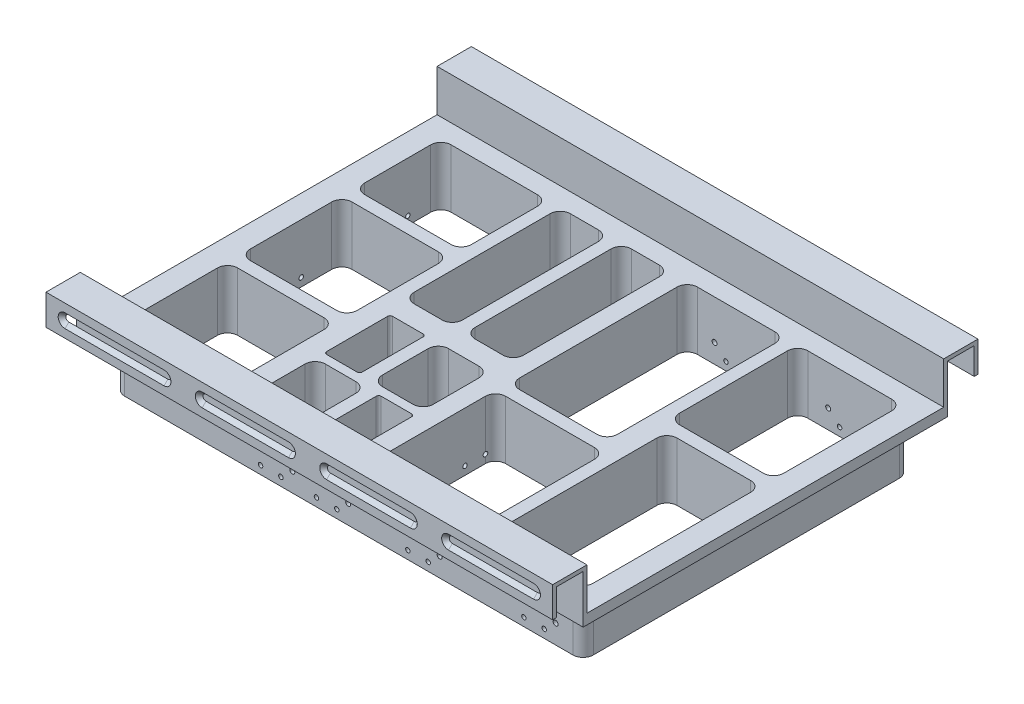
SolidWorks part; units mm, degrees
ref_plane "Front Plane" through (0, 0, 0) normal (0, 0, 1) x (1, 0, 0)
ref_plane "Top Plane" through (0, 0, 0) normal (0, 1, 0) x (1, 0, 0)
ref_plane "Right Plane" through (0, 0, 0) normal (1, 0, 0) x (0, 0, -1)
sketch "Sketch1" plane through (0, 0, 0) normal (0, 1, 0) x (1, 0, 0)
  line L1 (199.5, -143.5) -> (-199.5, -143.5)
  line L2 (199.5, -143.5) -> (199.5, 143.5)
  line L3 (199.5, 143.5) -> (-199.5, 143.5)
  line L4 (-199.5, -143.5) -> (-199.5, 143.5)
  line L5 (199.5, -143.5) -> (-199.5, 143.5) construction
  line L6 (199.5, 143.5) -> (-199.5, -143.5) construction
  point P0 (0, 0)
  dimension "D1" = 399
  dimension "D2" = 287
extrude "Boss-Extrude1" add sketch "Sketch1" along normal blind 53
sketch "Sketch3" plane through (0, 0, 0) normal (0, -1, 0) x (-1, 0, 0)
  line L23 (184.5, -128.5) -> (184.5, 128.5)
  line L24 (184.5, 128.5) -> (-184.5, 128.5)
  line L25 (-184.5, 128.5) -> (-184.5, -128.5)
  line L26 (-184.5, -128.5) -> (184.5, -128.5)
  line L27 (184.5, -128.5) -> (184.5, 128.5)
  line L28 (184.5, 128.5) -> (-184.5, 128.5)
  line L29 (-184.5, 128.5) -> (-184.5, -128.5)
  line L30 (-184.5, -128.5) -> (184.5, -128.5)
  dimension "D1" = 15
extrude "Cut-Extrude2" cut sketch "Sketch3" against normal blind 45 flip side to cut
sketch "Sketch2" plane through (0, 53, 0) normal (0, 1, 0) x (1, 0, 0)
  line L1 (-173.5, -125.5) -> (-105.5, -125.5)
  line L2 (-181.5, -117.5) -> (-181.5, -50.5)
  line L3 (-173.5, -42.5) -> (-105.5, -42.5)
  line L4 (-97.5, -117.5) -> (-97.5, -50.5)
  line L5 (-173.5, -32.5) -> (-105.5, -32.5)
  line L6 (-181.5, -24.5) -> (-181.5, 39.5)
  line L7 (-173.5, 47.5) -> (-105.5, 47.5)
  line L8 (-181.5, 125.5) -> (-181.5, -125.5)
  line L9 (-181.5, -125.5) -> (181.5, -125.5)
  line L10 (181.5, -125.5) -> (181.5, 125.5)
  line L11 (181.5, 125.5) -> (-181.5, 125.5)
  line L12 (-181.5, 125.5) -> (-181.5, -125.5) construction
  line L13 (-181.5, -125.5) -> (181.5, -125.5) construction
  line L14 (181.5, -125.5) -> (181.5, 125.5) construction
  line L15 (181.5, 125.5) -> (-181.5, 125.5) construction
  line L16 (-97.5, -24.5) -> (-97.5, 39.5)
  line L17 (-173.5, 125.5) -> (-105.5, 125.5)
  line L18 (-181.5, 117.5) -> (-181.5, 65.5)
  line L19 (-173.5, 57.5) -> (-105.5, 57.5)
  line L20 (-97.5, 117.5) -> (-97.5, 65.5)
  line L21 (173.5, -125.5) -> (115.5, -125.5)
  line L22 (181.5, -117.5) -> (181.5, 6.5)
  line L23 (173.5, 14.5) -> (115.5, 14.5)
  line L24 (107.5, -117.5) -> (107.5, 6.5)
  line L25 (173.5, 125.5) -> (107.5, 125.5)
  line L26 (181.5, 117.5) -> (181.5, 32.5)
  line L27 (173.5, 24.5) -> (107.5, 24.5)
  line L28 (99.5, 117.5) -> (99.5, 32.5)
  line L29 (81.5, 125.5) -> (20.5, 125.5)
  line L30 (89.5, 117.5) -> (89.5, -6.5)
  line L31 (81.5, -14.5) -> (20.5, -14.5)
  line L32 (12.5, 117.5) -> (12.5, -6.5)
  line L33 (-9.5, 125.5) -> (-31.5, 125.5)
  line L34 (-1.5, 117.5) -> (-1.5, 10.5)
  line L35 (-9.5, 2.5) -> (-31.5, 2.5)
  line L36 (-39.5, 117.5) -> (-39.5, 10.5)
  line L37 (-57.5, 125.5) -> (-79.5, 125.5)
  line L38 (-49.5, 117.5) -> (-49.5, 10.5)
  line L39 (-57.5, 2.5) -> (-79.5, 2.5)
  line L40 (-87.5, 117.5) -> (-87.5, 10.5)
  line L41 (-79.5, -14.5) -> (-55.5, -14.5)
  line L42 (-81.5, -16.5) -> (-81.5, -64.5)
  line L43 (-79.5, -66.5) -> (-55.5, -66.5)
  line L44 (-53.5, -16.5) -> (-53.5, -64.5)
  line L45 (-73.5, -125.5) -> (-49.5, -125.5)
  line L46 (-81.5, -117.5) -> (-81.5, -81.5)
  line L47 (-73.5, -73.5) -> (-49.5, -73.5)
  line L48 (-41.5, -117.5) -> (-41.5, -81.5)
  line L49 (-35.5, -14.5) -> (-11.5, -14.5)
  line L50 (-43.5, -22.5) -> (-43.5, -58.5)
  line L51 (-35.5, -66.5) -> (-11.5, -66.5)
  line L52 (-3.5, -22.5) -> (-3.5, -58.5)
  line L53 (-29.5, -73.5) -> (-5.5, -73.5)
  line L54 (-31.5, -75.5) -> (-31.5, -123.5)
  line L55 (-29.5, -125.5) -> (-5.5, -125.5)
  line L56 (-3.5, -75.5) -> (-3.5, -123.5)
  line L57 (89.5, -125.5) -> (19.5, -125.5)
  line L58 (97.5, -117.5) -> (97.5, -32.5)
  line L59 (89.5, -24.5) -> (19.5, -24.5)
  line L60 (11.5, -117.5) -> (11.5, -32.5)
  arc A0 (-79.5, 125.5) -> (-87.5, 117.5) centre (-79.5, 117.5) ccw
  arc A1 (-79.5, 2.5) -> (-87.5, 10.5) centre (-79.5, 10.5) cw
  arc A2 (-49.5, 10.5) -> (-57.5, 2.5) centre (-57.5, 10.5) cw
  arc A3 (-57.5, 125.5) -> (-49.5, 117.5) centre (-57.5, 117.5) cw
  arc A4 (-31.5, 125.5) -> (-39.5, 117.5) centre (-31.5, 117.5) ccw
  arc A5 (-31.5, 2.5) -> (-39.5, 10.5) centre (-31.5, 10.5) cw
  arc A6 (-1.5, 10.5) -> (-9.5, 2.5) centre (-9.5, 10.5) cw
  arc A7 (-9.5, 125.5) -> (-1.5, 117.5) centre (-9.5, 117.5) cw
  arc A8 (20.5, 125.5) -> (12.5, 117.5) centre (20.5, 117.5) ccw
  arc A9 (20.5, -14.5) -> (12.5, -6.5) centre (20.5, -6.5) cw
  arc A10 (89.5, -6.5) -> (81.5, -14.5) centre (81.5, -6.5) cw
  arc A11 (81.5, 125.5) -> (89.5, 117.5) centre (81.5, 117.5) cw
  arc A12 (107.5, 125.5) -> (99.5, 117.5) centre (107.5, 117.5) ccw
  arc A13 (173.5, 125.5) -> (181.5, 117.5) centre (173.5, 117.5) cw
  arc A14 (181.5, 32.5) -> (173.5, 24.5) centre (173.5, 32.5) cw
  arc A15 (107.5, 24.5) -> (99.5, 32.5) centre (107.5, 32.5) cw
  arc A16 (115.5, 14.5) -> (107.5, 6.5) centre (115.5, 6.5) ccw
  arc A17 (181.5, 6.5) -> (173.5, 14.5) centre (173.5, 6.5) ccw
  arc A18 (173.5, -125.5) -> (181.5, -117.5) centre (173.5, -117.5) ccw
  arc A19 (115.5, -125.5) -> (107.5, -117.5) centre (115.5, -117.5) cw
  arc A20 (89.5, -125.5) -> (97.5, -117.5) centre (89.5, -117.5) ccw
  arc A21 (97.5, -32.5) -> (89.5, -24.5) centre (89.5, -32.5) ccw
  arc A22 (19.5, -24.5) -> (11.5, -32.5) centre (19.5, -32.5) ccw
  arc A23 (19.5, -125.5) -> (11.5, -117.5) centre (19.5, -117.5) cw
  arc A28 (-43.5, -58.5) -> (-35.5, -66.5) centre (-35.5, -58.5) ccw
  arc A29 (-11.5, -66.5) -> (-3.5, -58.5) centre (-11.5, -58.5) ccw
  arc A30 (-11.5, -14.5) -> (-3.5, -22.5) centre (-11.5, -22.5) cw
  arc A31 (-35.5, -14.5) -> (-43.5, -22.5) centre (-35.5, -22.5) ccw
  arc A36 (-49.5, -73.5) -> (-41.5, -81.5) centre (-49.5, -81.5) cw
  arc A37 (-49.5, -125.5) -> (-41.5, -117.5) centre (-49.5, -117.5) ccw
  arc A38 (-73.5, -125.5) -> (-81.5, -117.5) centre (-73.5, -117.5) cw
  arc A39 (-81.5, -81.5) -> (-73.5, -73.5) centre (-73.5, -81.5) cw
  arc A40 (-105.5, -42.5) -> (-97.5, -50.5) centre (-105.5, -50.5) cw
  arc A41 (-105.5, -125.5) -> (-97.5, -117.5) centre (-105.5, -117.5) ccw
  arc A42 (-173.5, -125.5) -> (-181.5, -117.5) centre (-173.5, -117.5) cw
  arc A43 (-181.5, -50.5) -> (-173.5, -42.5) centre (-173.5, -50.5) cw
  arc A44 (-105.5, 47.5) -> (-97.5, 39.5) centre (-105.5, 39.5) cw
  arc A45 (-105.5, -32.5) -> (-97.5, -24.5) centre (-105.5, -24.5) ccw
  arc A46 (-173.5, -32.5) -> (-181.5, -24.5) centre (-173.5, -24.5) cw
  arc A47 (-181.5, 39.5) -> (-173.5, 47.5) centre (-173.5, 39.5) cw
  arc A48 (-105.5, 125.5) -> (-97.5, 117.5) centre (-105.5, 117.5) cw
  arc A49 (-105.5, 57.5) -> (-97.5, 65.5) centre (-105.5, 65.5) ccw
  arc A50 (-181.5, 65.5) -> (-173.5, 57.5) centre (-173.5, 65.5) ccw
  arc A51 (-173.5, 125.5) -> (-181.5, 117.5) centre (-173.5, 117.5) ccw
  arc A52 (-81.5, -16.5) -> (-79.5, -14.5) centre (-79.5, -16.5) cw
  arc A53 (-79.5, -66.5) -> (-81.5, -64.5) centre (-79.5, -64.5) cw
  arc A54 (-53.5, -64.5) -> (-55.5, -66.5) centre (-55.5, -64.5) cw
  arc A55 (-55.5, -14.5) -> (-53.5, -16.5) centre (-55.5, -16.5) cw
  arc A56 (-3.5, -75.5) -> (-5.5, -73.5) centre (-5.5, -75.5) ccw
  arc A57 (-5.5, -125.5) -> (-3.5, -123.5) centre (-5.5, -123.5) ccw
  arc A58 (-31.5, -123.5) -> (-29.5, -125.5) centre (-29.5, -123.5) ccw
  arc A59 (-31.5, -75.5) -> (-29.5, -73.5) centre (-29.5, -75.5) cw
  point P54 (-87.5, 125.5)
  point P57 (-87.5, 2.5)
  point P62 (-49.5, 125.5)
  point P65 (-39.5, 125.5)
  point P72 (-1.5, 125.5)
  point P75 (12.5, 125.5)
  point P82 (89.5, 125.5)
  point P85 (99.5, 125.5)
  point P91 (181.5, 24.5)
  point P103 (107.5, -125.5)
  point P106 (97.5, -125.5)
  point P109 (97.5, -24.5)
  point P114 (11.5, -125.5)
  point P119 (-3.5, -125.5)
  point P122 (-31.5, -125.5)
  point P127 (-43.5, -66.5)
  point P130 (-3.5, -66.5)
  point P139 (-81.5, -14.5)
  point P142 (-81.5, -66.5)
  point P149 (-41.5, -125.5)
  point P152 (-81.5, -125.5)
  point P155 (-81.5, -73.5)
  point P171 (-181.5, -32.5)
  point P174 (-181.5, 47.5)
  point P177 (-97.5, 125.5)
  point P182 (-181.5, 57.5)
  point P188 (-81.5, -14.5)
  point P191 (-81.5, -66.5)
  point P200 (-3.5, -125.5)
  point P203 (-31.5, -125.5)
  dimension "D31" = 8
  dimension "D32" = 8
  dimension "D33" = 8
  dimension "D34" = 2
  dimension "D35" = 2
  dimension "D2" = 74
  dimension "D3" = 82
  dimension "D4" = 101
  dimension "D5" = 10
  dimension "D6" = 86
  dimension "D7" = 10
  dimension "D8" = 15
  dimension "D9" = 28
  dimension "D10" = 40
  dimension "D11" = 52
  dimension "D12" = 52
  dimension "D13" = 77
  dimension "D14" = 38
  dimension "D15" = 38
  dimension "D16" = 84
  dimension "D17" = 68
  dimension "D18" = 80
  dimension "D19" = 10
  dimension "D20" = 10
  dimension "D21" = 7
  dimension "D22" = 10
  dimension "D23" = 101
  dimension "D24" = 10
  dimension "D25" = 10
  dimension "D26" = 123
  dimension "D27" = 10
  dimension "D28" = 10
  dimension "D29" = 40
  dimension "D30" = 10
  dimension "D1" = 18
extrude "Mini bin cuts" cut sketch "Sketch2" against normal blind 46
fillet "Fillet1" radius 8 4 edges at (-184.5, 22.5, -128.5) (184.5, 22.5, -128.5) (184.5, 22.5, 128.5) (-184.5, 22.5, 128.5)
sketch "Sketch6" plane through (-184.5, 0, 0) normal (-1, 0, 0) x (0, 0, 1)
  line L0 (128.5, 45) -> (128.5, 0) construction
  line L1 (-128.5, 0) -> (128.5, 0)
  line L2 (-128.5, 0) -> (-128.5, 7)
  line L3 (-128.5, 7) -> (128.5, 7)
  line L4 (128.5, 0) -> (128.5, 7)
  dimension "D1" = 7
extrude "Cut-Extrude5" cut sketch "Sketch6" against normal through all
sketch "Sketch7" plane through (-184.5, 0, 0) normal (-1, 0, 0) x (0, 0, 1)
  line L0 (-120.5, 13.5) -> (120.5, 13.5) construction
  line L1 (-120.5, 45) -> (-120.5, 7) construction
  line L2 (120.5, 7) -> (120.5, 45) construction
  line L3 (120.5, 7) -> (-120.5, 7) construction
  line L4 (-91.5, 13.5) -> (-91.5, 45) construction
  line L5 (120.5, 45) -> (-120.5, 45) construction
  line L6 (-7.5, 13.5) -> (-7.5, 45) construction
  line L7 (84, 13.5) -> (84, 45) construction
  circle A0 centre (-99.5, 13.5) radius 1.75
  circle A1 centre (-83.5, 13.5) radius 1.75
  circle A2 centre (-15.5, 13.5) radius 1.75
  circle A3 centre (76, 13.5) radius 1.75
  circle A4 centre (0.5, 13.5) radius 1.75
  circle A5 centre (92, 13.5) radius 1.75
  circle A6 centre (-74.5, 21.963) radius 1.95
  circle A7 centre (101, 21.963) radius 1.95
  circle A8 centre (9.5, 21.963) radius 1.95
  dimension "D2" = 36.5
  dimension "D5" = 3.5
  dimension "D7" = 3.5
  dimension "D9" = 3.5
  dimension "D11" = 3.9
  dimension "D12" = 3.9
  dimension "D13" = 3.9
  dimension "D1" = 6.5
  dimension "D3" = 29
  dimension "D4" = 113
  dimension "D6" = 8
  dimension "D8" = 8
  dimension "D10" = 8
  dimension "D14" = 17
  dimension "D15" = 17
  dimension "D16" = 17
  dimension "D17" = 8.463
  dimension "D18" = 8.463
  dimension "D19" = 8.463
extrude "Holes Lids 1,2,3" cut sketch "Sketch7" against normal up to surface (3 mm away) up to face at (-181.5, 30, 84)
sketch "Sketch8" plane through (0, 0, 128.5) normal (0, 0, 1) x (1, 0, 0)
  line L0 (-176.5, 13.5) -> (176.5, 13.5) construction
  line L1 (-176.5, 45) -> (-176.5, 7) construction
  line L2 (176.5, 7) -> (176.5, 45) construction
  line L5 (-61.5, 45) -> (-61.5, 7) construction
  line L6 (176.5, 45) -> (-176.5, 45) construction
  line L7 (176.5, 7) -> (-176.5, 7) construction
  line L8 (-17.5, 45) -> (-17.5, 7) construction
  line L11 (145.896, 45) -> (145.896, 7) construction
  line L12 (54.5, 45) -> (54.5, 7) construction
  circle A0 centre (-69.5, 13.5) radius 1.75
  circle A1 centre (-25.5, 13.5) radius 1.75
  circle A2 centre (46.5, 13.5) radius 1.75
  circle A3 centre (137.896, 13.5) radius 1.75
  circle A4 centre (153.896, 13.5) radius 1.75
  circle A5 centre (62.5, 13.5) radius 1.75
  circle A6 centre (-9.5, 13.5) radius 1.75
  circle A7 centre (-53.5, 13.5) radius 1.75
  circle A8 centre (-44.5, 21.96) radius 1.95
  circle A9 centre (-0.5, 21.96) radius 1.95
  circle A10 centre (71.5, 21.96) radius 1.95
  circle A11 centre (162.896, 21.96) radius 1.95
  dimension "D5" = 3.5
  dimension "D6" = 3.5
  dimension "D7" = 3.5
  dimension "D8" = 3.5
  dimension "D14" = 3.9
  dimension "D16" = 8.46
  dimension "D17" = 17
  dimension "D18" = 8.46
  dimension "D19" = 17
  dimension "D20" = 8.46
  dimension "D22" = 8.46
  dimension "D1" = 115
  dimension "D2" = 159
  dimension "D3" = 6.5
  dimension "D4" = 122
  dimension "D9" = 8
  dimension "D10" = 8
  dimension "D11" = 8
  dimension "D12" = 8
  dimension "D13" = 30.604
  dimension "D15" = 17
  dimension "D21" = 17
extrude "Holes Lids 8,9,12,13" cut sketch "Sketch8" against normal up to surface (3 mm away) up to face at (54.5, 30, 125.5)
sketch "Sketch9" plane through (0, 0, -128.5) normal (0, 0, -1) x (-1, 0, 0)
  line L0 (-176.5, 13.5) -> (176.5, 13.5) construction
  line L1 (-176.5, 45) -> (-176.5, 7) construction
  line L2 (176.5, 7) -> (176.5, 45) construction
  line L3 (-140.5, 45) -> (-140.5, 7) construction
  line L4 (176.5, 45) -> (-176.5, 45) construction
  line L5 (-176.5, 7) -> (176.5, 7) construction
  line L7 (20.5, 45) -> (20.5, 7) construction
  line L8 (199.5, 45) -> (-199.5, 45) construction
  line L9 (68.5, 45) -> (68.5, 7) construction
  line L10 (-51, 45) -> (-51, 7) construction
  circle A0 centre (-148.5, 13.5) radius 1.75
  circle A1 centre (-59, 13.5) radius 1.75
  circle A2 centre (12.5, 13.5) radius 1.75
  circle A3 centre (60.5, 13.5) radius 1.75
  circle A4 centre (-132.5, 13.5) radius 1.75
  circle A5 centre (-43, 13.5) radius 1.75
  circle A6 centre (28.5, 13.5) radius 1.75
  circle A7 centre (76.5, 13.5) radius 1.75
  circle A8 centre (-123.5, 21.96) radius 1.95
  circle A9 centre (-34, 21.96) radius 1.95
  circle A10 centre (37.5, 21.96) radius 1.95
  circle A11 centre (85.5, 21.96) radius 1.95
  dimension "D6" = 3.5
  dimension "D10" = 8
  dimension "D11" = 3.5
  dimension "D12" = 3.5
  dimension "D13" = 3.5
  dimension "D14" = 3.9
  dimension "D15" = 3.9
  dimension "D16" = 3.9
  dimension "D17" = 17
  dimension "D19" = 17
  dimension "D20" = 8.46
  dimension "D21" = 8.46
  dimension "D22" = 8.46
  dimension "D23" = 8.46
  dimension "D24" = 3.9
  dimension "D25" = 17
  dimension "D1" = 6.5
  dimension "D2" = 36
  dimension "D3" = 125.5
  dimension "D4" = 197
  dimension "D5" = 245
  dimension "D7" = 8
  dimension "D8" = 8
  dimension "D9" = 8
  dimension "D18" = 17
extrude "Holes Lids 4,5,10,11" cut sketch "Sketch9" against normal up to surface (3 mm away) up to face at (51, 30, -125.5)
sketch "Sketch11" plane through (-3.5, 0, 0) normal (-1, 0, 0) x (0, 0, 1)
  line L0 (22.5, 13.5) -> (58.5, 13.5) construction
  line L1 (22.5, 7) -> (22.5, 53) construction
  line L2 (58.5, 7) -> (58.5, 53) construction
  line L3 (40.5, 7) -> (40.5, 53) construction
  line L4 (58.5, 7) -> (22.5, 7) construction
  line L5 (22.5, 53) -> (58.5, 53) construction
  circle A0 centre (32.5, 13.5) radius 1.75
  circle A1 centre (48.5, 13.5) radius 1.75
  dimension "D2" = 3.5
  dimension "D1" = 6.5
  dimension "D3" = 8
extrude "Hole Lid 7" cut sketch "Sketch11" against normal up to next
sketch "Sketch12" plane through (-81.5, 0, 0) normal (1, 0, 0) x (0, 0, -1)
  line L0 (-64.5, 13.5) -> (-16.5, 13.5) construction
  line L1 (-64.5, 7) -> (-64.5, 53) construction
  line L2 (-16.5, 7) -> (-16.5, 53) construction
  line L3 (-40.5, 7) -> (-40.5, 53) construction
  line L5 (-16.5, 7) -> (-64.5, 7) construction
  line L6 (-16.5, 53) -> (-64.5, 53) construction
  circle A0 centre (-48.5, 13.5) radius 1.75
  circle A1 centre (-32.5, 13.5) radius 1.75
  dimension "D2" = 3.5
  dimension "D1" = 6.5
  dimension "D3" = 8
extrude "Hole Lid 6" cut sketch "Sketch12" against normal blind 15
sketch "Sketch15" plane through (-199.5, 0, 0) normal (-1, 0, 0) x (0, 0, 1)
  line L0 (143.5, 53) -> (143.5, 83)
  line L1 (143.5, 83) -> (164.5, 83)
  line L2 (164.5, 83) -> (164.5, 62)
  line L3 (164.5, 62) -> (167.5, 62)
  line L4 (167.5, 62) -> (167.5, 86)
  line L5 (167.5, 86) -> (140.5, 86)
  line L6 (140.5, 86) -> (140.5, 53)
  line L7 (-143.5, 53) -> (143.5, 53) construction
  line L8 (140.5, 53) -> (143.5, 53)
  line L9 (0, 0) -> (0, 7) construction
  line L10 (120.5, 7) -> (-120.5, 7) construction
  line L11 (-140.5, 53) -> (-143.5, 53)
  line L12 (-140.5, 86) -> (-140.5, 53)
  line L13 (-167.5, 86) -> (-140.5, 86)
  line L14 (-167.5, 62) -> (-167.5, 86)
  line L15 (-164.5, 62) -> (-167.5, 62)
  line L16 (-164.5, 83) -> (-164.5, 62)
  line L17 (-143.5, 83) -> (-164.5, 83)
  line L18 (-143.5, 53) -> (-143.5, 83)
  dimension "D1" = 21
  dimension "D2" = 21
  dimension "D3" = 30
  dimension "D4" = 3
  dimension "D5" = 3
  dimension "D6" = 3
extrude "Boss-Extrude3" add sketch "Sketch15" against normal up to surface (399 mm away) up to face at (199.5, 49, 0)
sketch "Split Lines" plane through (0, 86, 0) normal (0, 1, 0) x (1, 0, 0)
  line L0 (-199.5, 0) -> (199.5, 0) construction
  line L1 (-97.5, 117.5) -> (-97.5, 65.5) construction
  line L2 (199.5, 140.5) -> (-199.5, 140.5) construction
  line L3 (-199.5, 140.5) -> (-199.5, -140.5) construction
  line L4 (199.5, -140.5) -> (199.5, 140.5) construction
  line L5 (-93.5, 167.5) -> (-93.5, 104.5)
  line L6 (199.5, 143.5) -> (-199.5, 143.5) construction
  line L7 (-199.5, -143.5) -> (199.5, -143.5) construction
  line L8 (-90.25, -114.5) -> (-91.5, -114.5)
  line L9 (-89.5, -117.75) -> (-89.5, -115.25)
  line L10 (-88.25, -118.5) -> (-88.75, -118.5)
  line L11 (-87.5, -105.25) -> (-87.5, -117.75)
  line L12 (-88.75, -104.5) -> (-88.25, -104.5)
  line L13 (-89.5, -107.75) -> (-89.5, -105.25)
  line L14 (-93.5, 45) -> (-92.5, 45)
  line L15 (-91.75, 45.75) -> (-91.75, 48.25)
  line L16 (-91, 49) -> (-90.5, 49)
  line L17 (-89.75, 48.25) -> (-89.75, 35.75)
  line L18 (-90.5, 35) -> (-91, 35)
  line L19 (-91.75, 35.75) -> (-91.75, 38.25)
  line L20 (-92.5, 39) -> (-93.5, 39)
  line L21 (-93.5, 39) -> (-93.5, -8)
  line L22 (-91.5, -167.5) -> (-91.5, -114.5)
  line L23 (-81.5, -117.5) -> (-81.5, -81.5) construction
  line L24 (-139.5, -32.5) -> (-139.5, -42.5) construction
  line L25 (-173.5, -42.5) -> (-105.5, -42.5) construction
  line L26 (-163.5, -37) -> (-163.5, -36)
  line L27 (-157.5, -36) -> (-157.5, -37)
  line L28 (-156.75, -37.75) -> (-154.25, -37.75)
  line L29 (-153.5, -38.5) -> (-153.5, -39)
  line L30 (-154.25, -39.75) -> (-166.75, -39.75)
  line L31 (-121.5, -36) -> (-121.5, -37)
  line L32 (-122.25, -37.75) -> (-124.75, -37.75)
  line L33 (-125.5, -38.5) -> (-125.5, -39)
  line L34 (-124.75, -39.75) -> (-112.25, -39.75)
  line L35 (-111.5, -39) -> (-111.5, -38.5)
  line L36 (-112.25, -37.75) -> (-114.75, -37.75)
  line L37 (-93.5, 98.5) -> (-93.5, 45)
  line L38 (-115.5, -37) -> (-115.5, -36)
  line L39 (6.5, 167.5) -> (6.5, 104.5)
  line L40 (-1.5, 117.5) -> (-1.5, 10.5) construction
  line L41 (6.5, 104.5) -> (5.5, 104.5)
  line L42 (4.75, 105.25) -> (4.75, 107.75)
  line L43 (4, 108.5) -> (3.5, 108.5)
  line L44 (2.75, 107.75) -> (2.75, 95.25)
  line L45 (3.5, 94.5) -> (4, 94.5)
  line L46 (4.75, 95.25) -> (4.75, 97.75)
  line L47 (5.5, 98.5) -> (6.5, 98.5)
  line L48 (7.5, -39) -> (6.5, -39)
  line L49 (8.25, -35.75) -> (8.25, -38.25)
  line L50 (6.5, 45) -> (8.25, 45)
  line L51 (8.25, 45) -> (8.25, 48.25)
  line L52 (9, 49) -> (9.5, 49)
  line L53 (10.25, 48.25) -> (10.25, 35.75)
  line L54 (9.5, 35) -> (9, 35)
  line L55 (8.25, 35.75) -> (8.25, 38.25)
  line L56 (7.5, 39) -> (7.25, 39)
  line L57 (9.5, -35) -> (9, -35)
  line L58 (10.25, -48.25) -> (10.25, -35.75)
  line L59 (9, -49) -> (9.5, -49)
  line L60 (8.25, -45.75) -> (8.25, -48.25)
  line L61 (6.5, -45) -> (7.5, -45)
  line L62 (5.5, -98.5) -> (6.5, -98.5)
  line L63 (4.75, -95.25) -> (4.75, -97.75)
  line L64 (3.5, -94.5) -> (4, -94.5)
  line L65 (2.75, -107.75) -> (2.75, -95.25)
  line L66 (4, -108.5) -> (3.5, -108.5)
  line L67 (4.75, -104.5) -> (4.75, -107.75)
  line L68 (6.5, -104.5) -> (4.75, -104.5)
  line L69 (94.5, 167.5) -> (94.5, 104.5)
  line L70 (-167.5, -39) -> (-167.5, -38.5)
  line L71 (102.5, 19.5) -> (102.5, -39)
  line L72 (89.5, 117.5) -> (89.5, -6.5) construction
  line L73 (107.5, -117.5) -> (107.5, 6.5) construction
  line L74 (94.5, 104.5) -> (93.5, 104.5)
  line L75 (92.75, 105.25) -> (92.75, 107.75)
  line L76 (92, 108.5) -> (91.5, 108.5)
  line L77 (90.75, 107.75) -> (90.75, 95.25)
  line L78 (91.5, 94.5) -> (92, 94.5)
  line L79 (92.75, 95.25) -> (92.75, 97.75)
  line L80 (93.5, 98.5) -> (94.5, 98.5)
  line L81 (94.5, 45) -> (95.5, 45)
  line L82 (96.25, 45.75) -> (96.25, 48.25)
  line L83 (97, 49) -> (97.5, 49)
  line L84 (98.25, 48.25) -> (98.25, 35.75)
  line L85 (97.5, 35) -> (97, 35)
  line L86 (96.25, 35.75) -> (96.25, 38.25)
  line L87 (95.5, 39) -> (94.5, 39)
  line L88 (102.5, -39) -> (103.5, -39)
  line L89 (104.25, -38.25) -> (104.25, -35.75)
  line L90 (105, -35) -> (105.5, -35)
  line L91 (106.25, -35.75) -> (106.25, -48.25)
  line L92 (105.5, -49) -> (105, -49)
  line L93 (104.25, -48.25) -> (104.25, -45.75)
  line L94 (103.5, -45) -> (102.5, -45)
  line L95 (102.5, -98.5) -> (101.5, -98.5)
  line L96 (100.75, -97.75) -> (100.75, -95.25)
  line L97 (100, -94.5) -> (99.5, -94.5)
  line L98 (98.75, -95.25) -> (98.75, -107.75)
  line L99 (99.5, -108.5) -> (100, -108.5)
  line L100 (100.75, -107.75) -> (100.75, -105.25)
  line L101 (101.5, -104.5) -> (102.5, -104.5)
  line L102 (6.5, 98.5) -> (6.5, 45)
  line L103 (6.5, 38.25) -> (6.5, -39)
  line L104 (6.5, -45) -> (6.5, -98.5)
  line L105 (6.5, -104.5) -> (6.5, -167.5)
  line L106 (102.5, -104.5) -> (102.5, -167.5)
  line L107 (102.5, -45) -> (102.5, -98.5)
  line L108 (94.5, 39) -> (94.5, 27.5)
  line L109 (94.5, 98.5) -> (94.5, 45)
  line L110 (199.5, 19.5) -> (175.5, 19.5)
  line L111 (-91.5, -56.5) -> (-90.25, -56.5)
  line L112 (102.5, -18) -> (76, -18)
  line L113 (-89.5, -55.75) -> (-89.5, -53.25)
  line L114 (6.5, -9) -> (-17.5, -9)
  line L115 (-88.75, -52.5) -> (-88.25, -52.5)
  line L116 (-91.5, -36) -> (-115.5, -36)
  line L117 (-173.5, -32.5) -> (-105.5, -32.5) construction
  line L118 (-199.5, 140.5) -> (-199.5, -140.5) construction
  line L119 (-87.5, -53.25) -> (-87.5, -65.75)
  line L120 (-88.25, -66.5) -> (-88.75, -66.5)
  line L121 (-89.5, -65.75) -> (-89.5, -63.25)
  line L122 (-90.25, -62.5) -> (-91.5, -62.5)
  line L123 (199.5, -140.5) -> (-199.5, -140.5) construction
  line L124 (173.5, 24.5) -> (107.5, 24.5) construction
  line L125 (89.5, -24.5) -> (19.5, -24.5) construction
  line L126 (-91.5, -108.5) -> (-91.5, -62.5)
  line L127 (-163.5, -36) -> (-199.5, -36)
  line L128 (-121.5, -36) -> (-157.5, -36)
  line L129 (-23.5, -9) -> (-61.5, -9)
  line L130 (-67.5, -9) -> (-91.5, -9)
  line L131 (-91.5, -56.5) -> (-91.5, -9)
  line L132 (-42.5, -9) -> (-42.5, 0) construction
  line L133 (199.5, -140.5) -> (-199.5, -140.5) construction
  line L134 (-61.5, -9) -> (-61.5, -7.75)
  line L135 (-60.75, -7) -> (-58.25, -7)
  line L136 (-57.5, -6.25) -> (-57.5, -5.75)
  line L137 (-58.25, -5) -> (-70.75, -5)
  line L138 (-71.5, -5.75) -> (-71.5, -6.25)
  line L139 (-70.75, -7) -> (-68.25, -7)
  line L140 (-67.5, -7.75) -> (-67.5, -9)
  line L141 (-92.5, 98.5) -> (-93.5, 98.5)
  line L142 (-91.75, 95.25) -> (-91.75, 97.75)
  line L143 (-90.5, 94.5) -> (-91, 94.5)
  line L144 (-89.75, 107.75) -> (-89.75, 95.25)
  line L145 (-91, 108.5) -> (-90.5, 108.5)
  line L146 (54.5, -18) -> (54.5, -14.5) construction
  line L147 (81.5, -14.5) -> (20.5, -14.5) construction
  line L148 (29.75, -19.75) -> (32.25, -19.75)
  line L149 (33, -19) -> (33, -18)
  line L150 (39, -18) -> (39, -19.75)
  line L151 (39, -19.75) -> (42.25, -19.75)
  line L152 (43, -20.5) -> (43, -21)
  line L153 (70, -18) -> (70, -19)
  line L154 (69.25, -19.75) -> (66.75, -19.75)
  line L155 (66, -20.5) -> (66, -21)
  line L156 (66.75, -21.75) -> (79.25, -21.75)
  line L157 (80, -21) -> (80, -20.5)
  line L158 (79.25, -19.75) -> (76.75, -19.75)
  line L159 (76, -19) -> (76, -18)
  line L160 (151, 19.5) -> (151, 24.5) construction
  line L161 (132.5, 19.5) -> (132.5, 18.5)
  line L162 (133.25, 17.75) -> (135.75, 17.75)
  line L163 (136.5, 17) -> (136.5, 16.5)
  line L164 (135.75, 15.75) -> (123.25, 15.75)
  line L165 (122.5, 16.5) -> (122.5, 17)
  line L166 (123.25, 17.75) -> (125.75, 17.75)
  line L167 (-166.75, -37.75) -> (-164.25, -37.75)
  line L168 (169.5, 19.5) -> (169.5, 18.5)
  line L169 (168.75, 17.75) -> (166.25, 17.75)
  line L170 (165.5, 17) -> (165.5, 16.5)
  line L171 (166.25, 15.75) -> (178.75, 15.75)
  line L172 (179.5, 16.5) -> (179.5, 17)
  line L173 (178.75, 17.75) -> (176.25, 17.75)
  line L174 (175.5, 18.5) -> (175.5, 19.5)
  line L175 (-91.75, 105.25) -> (-91.75, 107.75)
  line L176 (42.25, -21.75) -> (29.75, -21.75)
  line L177 (29, -21) -> (29, -20.5)
  line L178 (126.5, 18.5) -> (126.5, 19.5)
  line L179 (199.5, -167.5) -> (-199.5, -167.5) construction
  line L180 (199.5, 167.5) -> (-199.5, 167.5) construction
  line L181 (-79.5, -14.5) -> (-55.5, -14.5) construction
  line L182 (-92.5, -9) -> (-91.5, -9)
  line L183 (-17.5, -7.75) -> (-17.5, -9)
  line L184 (-14.25, -7) -> (-16.75, -7)
  line L185 (-13.5, -5.75) -> (-13.5, -6.25)
  line L186 (-26.75, -5) -> (-14.25, -5)
  line L187 (-27.5, -6.25) -> (-27.5, -5.75)
  line L188 (-24.25, -7) -> (-26.75, -7)
  line L189 (-23.5, -9) -> (-23.5, -7.75)
  line L190 (-93.5, 104.5) -> (-92.5, 104.5)
  line L191 (-91.5, -108.5) -> (-90.25, -108.5)
  line L192 (33, -18) -> (6.5, -18)
  line L193 (70, -18) -> (39, -18)
  line L194 (126.5, 19.5) -> (102.5, 19.5)
  line L195 (169.5, 19.5) -> (132.5, 19.5)
  line L196 (199.5, -140.5) -> (199.5, 140.5) construction
  arc A0 (102.5, 19.5) -> (94.5, 27.5) centre (102.5, 27.5) cw
  arc A1 (-92.5, -9) -> (-93.5, -8) centre (-92.5, -8) cw
  arc A2 (-112.25, -39.75) -> (-111.5, -39) centre (-112.25, -39) ccw
  arc A3 (-111.5, -38.5) -> (-112.25, -37.75) centre (-112.25, -38.5) ccw
  arc A4 (-114.75, -37.75) -> (-115.5, -37) centre (-114.75, -37) cw
  arc A5 (-121.5, -37) -> (-122.25, -37.75) centre (-122.25, -37) cw
  arc A6 (-125.5, -39) -> (-124.75, -39.75) centre (-124.75, -39) ccw
  arc A7 (-124.75, -37.75) -> (-125.5, -38.5) centre (-124.75, -38.5) ccw
  arc A8 (-153.5, -39) -> (-154.25, -39.75) centre (-154.25, -39) cw
  arc A9 (-154.25, -37.75) -> (-153.5, -38.5) centre (-154.25, -38.5) cw
  arc A10 (-157.5, -37) -> (-156.75, -37.75) centre (-156.75, -37) ccw
  arc A11 (-163.5, -37) -> (-164.25, -37.75) centre (-164.25, -37) cw
  arc A12 (-166.75, -39.75) -> (-167.5, -39) centre (-166.75, -39) cw
  arc A13 (-167.5, -38.5) -> (-166.75, -37.75) centre (-166.75, -38.5) cw
  arc A14 (-89.5, -107.75) -> (-90.25, -108.5) centre (-90.25, -107.75) cw
  arc A15 (-90.25, -114.5) -> (-89.5, -115.25) centre (-90.25, -115.25) cw
  arc A16 (-88.75, -118.5) -> (-89.5, -117.75) centre (-88.75, -117.75) cw
  arc A17 (-88.25, -118.5) -> (-87.5, -117.75) centre (-88.25, -117.75) ccw
  arc A18 (-87.5, -105.25) -> (-88.25, -104.5) centre (-88.25, -105.25) ccw
  arc A19 (-89.5, -105.25) -> (-88.75, -104.5) centre (-88.75, -105.25) cw
  arc A20 (-88.25, -66.5) -> (-87.5, -65.75) centre (-88.25, -65.75) ccw
  arc A21 (-88.75, -66.5) -> (-89.5, -65.75) centre (-88.75, -65.75) cw
  arc A22 (-89.5, -63.25) -> (-90.25, -62.5) centre (-90.25, -63.25) ccw
  arc A23 (-89.5, -55.75) -> (-90.25, -56.5) centre (-90.25, -55.75) cw
  arc A24 (-89.5, -53.25) -> (-88.75, -52.5) centre (-88.75, -53.25) cw
  arc A25 (-88.25, -52.5) -> (-87.5, -53.25) centre (-88.25, -53.25) cw
  arc A32 (-90.5, 49) -> (-89.75, 48.25) centre (-90.5, 48.25) cw
  arc A33 (-91.75, 48.25) -> (-91, 49) centre (-91, 48.25) cw
  arc A34 (-92.5, 45) -> (-91.75, 45.75) centre (-92.5, 45.75) ccw
  arc A35 (-89.75, 35.75) -> (-90.5, 35) centre (-90.5, 35.75) cw
  arc A36 (-91, 35) -> (-91.75, 35.75) centre (-91, 35.75) cw
  arc A37 (-91.75, 38.25) -> (-92.5, 39) centre (-92.5, 38.25) ccw
  arc A38 (-13.5, -5.75) -> (-14.25, -5) centre (-14.25, -5.75) ccw
  arc A39 (-14.25, -7) -> (-13.5, -6.25) centre (-14.25, -6.25) ccw
  arc A40 (-16.75, -7) -> (-17.5, -7.75) centre (-16.75, -7.75) ccw
  arc A41 (-23.5, -7.75) -> (-24.25, -7) centre (-24.25, -7.75) ccw
  arc A42 (-27.5, -6.25) -> (-26.75, -7) centre (-26.75, -6.25) ccw
  arc A43 (-27.5, -5.75) -> (-26.75, -5) centre (-26.75, -5.75) cw
  arc A44 (-57.5, -5.75) -> (-58.25, -5) centre (-58.25, -5.75) ccw
  arc A45 (-57.5, -6.25) -> (-58.25, -7) centre (-58.25, -6.25) cw
  arc A46 (-61.5, -7.75) -> (-60.75, -7) centre (-60.75, -7.75) cw
  arc A47 (-68.25, -7) -> (-67.5, -7.75) centre (-68.25, -7.75) cw
  arc A48 (-70.75, -7) -> (-71.5, -6.25) centre (-70.75, -6.25) cw
  arc A49 (-71.5, -5.75) -> (-70.75, -5) centre (-70.75, -5.75) cw
  arc A50 (7.25, 39) -> (6.5, 38.25) centre (7.25, 38.25) ccw
  arc A51 (8.25, 38.25) -> (7.5, 39) centre (7.5, 38.25) ccw
  arc A52 (9, 35) -> (8.25, 35.75) centre (9, 35.75) cw
  arc A53 (10.25, 35.75) -> (9.5, 35) centre (9.5, 35.75) cw
  arc A54 (9.5, 49) -> (10.25, 48.25) centre (9.5, 48.25) cw
  arc A55 (8.25, 48.25) -> (9, 49) centre (9, 48.25) cw
  arc A56 (2.75, 95.25) -> (3.5, 94.5) centre (3.5, 95.25) ccw
  arc A57 (4, 94.5) -> (4.75, 95.25) centre (4, 95.25) ccw
  arc A58 (4.75, 97.75) -> (5.5, 98.5) centre (5.5, 97.75) cw
  arc A59 (5.5, 104.5) -> (4.75, 105.25) centre (5.5, 105.25) cw
  arc A60 (3.5, 108.5) -> (2.75, 107.75) centre (3.5, 107.75) ccw
  arc A61 (4.75, 107.75) -> (4, 108.5) centre (4, 107.75) ccw
  arc A62 (4, -108.5) -> (4.75, -107.75) centre (4, -107.75) ccw
  arc A63 (2.75, -107.75) -> (3.5, -108.5) centre (3.5, -107.75) ccw
  arc A64 (3.5, -94.5) -> (2.75, -95.25) centre (3.5, -95.25) ccw
  arc A65 (4.75, -95.25) -> (4, -94.5) centre (4, -95.25) ccw
  arc A66 (5.5, -98.5) -> (4.75, -97.75) centre (5.5, -97.75) cw
  arc A67 (8.25, -45.75) -> (7.5, -45) centre (7.5, -45.75) ccw
  arc A68 (9, -49) -> (8.25, -48.25) centre (9, -48.25) cw
  arc A69 (10.25, -48.25) -> (9.5, -49) centre (9.5, -48.25) cw
  arc A70 (9.5, -35) -> (10.25, -35.75) centre (9.5, -35.75) cw
  arc A71 (8.25, -35.75) -> (9, -35) centre (9, -35.75) cw
  arc A72 (7.5, -39) -> (8.25, -38.25) centre (7.5, -38.25) ccw
  arc A73 (104.25, -45.75) -> (103.5, -45) centre (103.5, -45.75) ccw
  arc A74 (105, -49) -> (104.25, -48.25) centre (105, -48.25) cw
  arc A75 (106.25, -48.25) -> (105.5, -49) centre (105.5, -48.25) cw
  arc A76 (105.5, -35) -> (106.25, -35.75) centre (105.5, -35.75) cw
  arc A77 (104.25, -35.75) -> (105, -35) centre (105, -35.75) cw
  arc A78 (103.5, -39) -> (104.25, -38.25) centre (103.5, -38.25) ccw
  arc A79 (100.75, -105.25) -> (101.5, -104.5) centre (101.5, -105.25) cw
  arc A80 (100, -108.5) -> (100.75, -107.75) centre (100, -107.75) ccw
  arc A81 (98.75, -107.75) -> (99.5, -108.5) centre (99.5, -107.75) ccw
  arc A82 (99.5, -94.5) -> (98.75, -95.25) centre (99.5, -95.25) ccw
  arc A83 (100.75, -95.25) -> (100, -94.5) centre (100, -95.25) ccw
  arc A84 (101.5, -98.5) -> (100.75, -97.75) centre (101.5, -97.75) cw
  arc A85 (79.25, -21.75) -> (80, -21) centre (79.25, -21) ccw
  arc A86 (80, -20.5) -> (79.25, -19.75) centre (79.25, -20.5) ccw
  arc A87 (76.75, -19.75) -> (76, -19) centre (76.75, -19) cw
  arc A88 (70, -19) -> (69.25, -19.75) centre (69.25, -19) cw
  arc A89 (66, -21) -> (66.75, -21.75) centre (66.75, -21) ccw
  arc A90 (66.75, -19.75) -> (66, -20.5) centre (66.75, -20.5) ccw
  arc A91 (42.25, -19.75) -> (43, -20.5) centre (42.25, -20.5) cw
  arc A92 (43, -21) -> (42.25, -21.75) centre (42.25, -21) cw
  arc A93 (29.75, -21.75) -> (29, -21) centre (29.75, -21) cw
  arc A94 (29.75, -19.75) -> (29, -20.5) centre (29.75, -20.5) ccw
  arc A95 (32.25, -19.75) -> (33, -19) centre (32.25, -19) ccw
  arc A96 (176.25, 17.75) -> (175.5, 18.5) centre (176.25, 18.5) cw
  arc A97 (179.5, 17) -> (178.75, 17.75) centre (178.75, 17) ccw
  arc A98 (178.75, 15.75) -> (179.5, 16.5) centre (178.75, 16.5) ccw
  arc A99 (165.5, 16.5) -> (166.25, 15.75) centre (166.25, 16.5) ccw
  arc A100 (166.25, 17.75) -> (165.5, 17) centre (166.25, 17) ccw
  arc A101 (169.5, 18.5) -> (168.75, 17.75) centre (168.75, 18.5) cw
  arc A102 (132.5, 18.5) -> (133.25, 17.75) centre (133.25, 18.5) ccw
  arc A103 (135.75, 17.75) -> (136.5, 17) centre (135.75, 17) cw
  arc A104 (136.5, 16.5) -> (135.75, 15.75) centre (135.75, 16.5) cw
  arc A105 (123.25, 15.75) -> (122.5, 16.5) centre (123.25, 16.5) cw
  arc A106 (122.5, 17) -> (123.25, 17.75) centre (123.25, 17) cw
  arc A107 (125.75, 17.75) -> (126.5, 18.5) centre (125.75, 18.5) ccw
  arc A108 (92.75, 97.75) -> (93.5, 98.5) centre (93.5, 97.75) cw
  arc A109 (92, 94.5) -> (92.75, 95.25) centre (92, 95.25) ccw
  arc A110 (90.75, 95.25) -> (91.5, 94.5) centre (91.5, 95.25) ccw
  arc A111 (91.5, 108.5) -> (90.75, 107.75) centre (91.5, 107.75) ccw
  arc A112 (92.75, 107.75) -> (92, 108.5) centre (92, 107.75) ccw
  arc A113 (93.5, 104.5) -> (92.75, 105.25) centre (93.5, 105.25) cw
  arc A114 (96.25, 38.25) -> (95.5, 39) centre (95.5, 38.25) ccw
  arc A115 (97, 35) -> (96.25, 35.75) centre (97, 35.75) cw
  arc A116 (98.25, 35.75) -> (97.5, 35) centre (97.5, 35.75) cw
  arc A117 (97.5, 49) -> (98.25, 48.25) centre (97.5, 48.25) cw
  arc A118 (95.5, 45) -> (96.25, 45.75) centre (95.5, 45.75) ccw
  arc A119 (96.25, 48.25) -> (97, 49) centre (97, 48.25) cw
  arc A120 (-91.75, 97.75) -> (-92.5, 98.5) centre (-92.5, 97.75) ccw
  arc A121 (-91, 94.5) -> (-91.75, 95.25) centre (-91, 95.25) cw
  arc A122 (-89.75, 95.25) -> (-90.5, 94.5) centre (-90.5, 95.25) cw
  arc A123 (-90.5, 108.5) -> (-89.75, 107.75) centre (-90.5, 107.75) cw
  arc A124 (-91.75, 107.75) -> (-91, 108.5) centre (-91, 107.75) cw
  arc A125 (-92.5, 104.5) -> (-91.75, 105.25) centre (-92.5, 105.25) ccw
  point P20 (-89.75, 101.5)
  point P138 (-87.5, -59.5)
  point P141 (0, 0)
  point P144 (-93.5, 157.3635)
  point P145 (-93.5, 167.5)
  point P148 (0, 0)
  point P149 (6.5, 155.6454)
  point P150 (6.5, 167.5)
  point P151 (-87.5, -111.5)
  point P156 (0, 0)
  point P157 (94.5, 157.7999)
  point P158 (94.5, 167.5)
  point P162 (-13.5, -6)
  point P224 (-111.5, -39.75)
  point P229 (-111.5, -37.75)
  point P234 (-115.5, -37.75)
  point P237 (-121.5, -37.75)
  point P240 (-125.5, -39.75)
  point P243 (-125.5, -37.75)
  point P246 (-153.5, -39.75)
  point P249 (-153.5, -37.75)
  point P252 (-157.5, -37.75)
  point P255 (-163.5, -37.75)
  point P258 (-167.5, -39.75)
  point P261 (-167.5, -37.75)
  point P265 (0, 0)
  point P266 (-91.5, -157.0413)
  point P267 (-91.5, -167.5)
  point P268 (0, 0)
  point P269 (6.5, -155.2132)
  point P270 (6.5, -167.5)
  point P271 (0, 0)
  point P272 (102.5, -159.2429)
  point P273 (102.5, -167.5)
  point P279 (-89.5, -66.5)
  point P283 (-89.5, -62.5)
  point P287 (-89.5, -56.5)
  point P292 (-89.5, -52.5)
  point P296 (-87.5, -52.5)
  point P297 (0, 0)
  point P298 (-193.427, -36)
  point P299 (-199.5, -36)
  point P300 (0, 0)
  point P301 (191.7613, 19.5)
  point P302 (199.5, 19.5)
  point P314 (-89.75, 49)
  point P317 (-91.75, 49)
  point P320 (-91.75, 45)
  point P323 (-89.75, 35)
  point P326 (-91.75, 35)
  point P367 (6.5, 39)
  point P370 (8.25, 39)
  point P373 (8.25, 35)
  point P376 (10.25, 35)
  point P379 (10.25, 49)
  point P382 (8.25, 49)
  point P385 (2.75, 94.5)
  point P388 (4.75, 94.5)
  point P391 (4.75, 98.5)
  point P394 (4.75, 104.5)
  point P397 (2.75, 108.5)
  point P400 (4.75, 108.5)
  point P403 (4.75, -108.5)
  point P406 (2.75, -108.5)
  point P409 (2.75, -94.5)
  point P412 (4.75, -94.5)
  point P415 (4.75, -98.5)
  point P418 (8.25, -45)
  point P421 (8.25, -49)
  point P424 (10.25, -49)
  point P427 (10.25, -35)
  point P430 (8.25, -35)
  point P433 (8.25, -39)
  point P440 (106.25, -49)
  point P443 (106.25, -35)
  point P446 (104.25, -35)
  point P449 (104.25, -39)
  point P452 (100.75, -104.5)
  point P455 (100.75, -108.5)
  point P458 (98.75, -108.5)
  point P461 (98.75, -94.5)
  point P464 (100.75, -94.5)
  point P467 (100.75, -98.5)
  point P470 (80, -21.75)
  point P473 (80, -19.75)
  point P476 (76, -19.75)
  point P479 (70, -19.75)
  point P482 (66, -21.75)
  point P485 (66, -19.75)
  point P488 (43, -19.75)
  point P491 (43, -21.75)
  point P494 (29, -21.75)
  point P497 (29, -19.75)
  point P500 (33, -19.75)
  point P503 (175.5, 17.75)
  point P506 (179.5, 17.75)
  point P509 (179.5, 15.75)
  point P512 (165.5, 15.75)
  point P515 (165.5, 17.75)
  point P518 (169.5, 17.75)
  point P521 (132.5, 17.75)
  point P524 (136.5, 17.75)
  point P527 (136.5, 15.75)
  point P530 (122.5, 15.75)
  point P533 (122.5, 17.75)
  point P536 (126.5, 17.75)
  point P543 (90.75, 94.5)
  point P546 (90.75, 108.5)
  point P549 (92.75, 108.5)
  point P552 (92.75, 104.5)
  point P555 (96.25, 39)
  point P558 (96.25, 35)
  point P561 (98.25, 35)
  point P564 (98.25, 49)
  point P567 (96.25, 45)
  point P583 (-89.75, 42)
  point P617 (-91.75, 98.5)
  point P618 (-89.75, 94.5)
  point P619 (-89.75, 108.5)
  point P621 (-91.75, 108.5)
  point P622 (-91.75, 104.5)
  dimension "D30" = 8
  dimension "D31" = 10
  dimension "D64" = 2
  dimension "D65" = 0.75
  dimension "D66" = 2
  dimension "D68" = 14
  dimension "D60" = 5.5
  dimension "D61" = 0.75
  dimension "D59" = 1
  dimension "D67" = 0.75
  dimension "D74" = 0.75
  dimension "D87" = 0.75
  dimension "D88" = 0.75
  dimension "D89" = 0.75
  dimension "D90" = 0.75
  dimension "D92" = 0.75
  dimension "D94" = 4
  dimension "D96" = 42
  dimension "D97" = 1.75
  dimension "D98" = 2
  dimension "D102" = 0.75
  dimension "D78" = 4
  dimension "D77" = 0.75
  dimension "D84" = 0.75
  dimension "D1" = 4
  dimension "D8" = 1.75
  dimension "D9" = 14
  dimension "D10" = 2
  dimension "D11" = 6
  dimension "D12" = 2
  dimension "D13" = 4
  dimension "D14" = 2
  dimension "D15" = 8
  dimension "D16" = 14
  dimension "D17" = 2
  dimension "D18" = 1.75
  dimension "D19" = 6
  dimension "D20" = 4
  dimension "D21" = 35
  dimension "D22" = 14
  dimension "D23" = 6
  dimension "D24" = 2
  dimension "D25" = 1.75
  dimension "D26" = 4
  dimension "D27" = 35
  dimension "D28" = 5
  dimension "D29" = 5
  dimension "D32" = 14
  dimension "D33" = 6
  dimension "D34" = 2
  dimension "D35" = 1.75
  dimension "D36" = 2
  dimension "D37" = 4
  dimension "D38" = 35
  dimension "D39" = 14
  dimension "D40" = 6
  dimension "D41" = 2
  dimension "D42" = 1.75
  dimension "D43" = 4
  dimension "D44" = 35
  dimension "D45" = 14
  dimension "D46" = 6
  dimension "D47" = 2
  dimension "D48" = 1.75
  dimension "D49" = 4
  dimension "D50" = 1.75
  dimension "D51" = 35
  dimension "D52" = 14
  dimension "D53" = 6
  dimension "D54" = 2
  dimension "D55" = 1.75
  dimension "D56" = 4
  dimension "D57" = 35
  dimension "D58" = 3.5
  dimension "D62" = 5
  dimension "D63" = 6.5
  dimension "D69" = 6
  dimension "D70" = 4
  dimension "D71" = 2
  dimension "D72" = 1.75
  dimension "D73" = 20
  dimension "D75" = 2
  dimension "D76" = 6
  dimension "D79" = 29
  dimension "D80" = 4
  dimension "D81" = 6
  dimension "D82" = 2
  dimension "D83" = 2
  dimension "D85" = 4
  dimension "D86" = 108
  dimension "D91" = 6
  dimension "D93" = 14
  dimension "D95" = 24
  dimension "D99" = 6
  dimension "D100" = 14
  dimension "D101" = 39
  dimension "D103" = 7
  dimension "D104" = 49
  dimension "D105" = 48
  dimension "D106" = 14
  dimension "D107" = 6
  dimension "D108" = 4
  dimension "D109" = 2
  dimension "D110" = 1.75
  dimension "D111" = 22.5
  dimension "D112" = 48.5
  dimension "D119" = 14
  dimension "D120" = 1.75
  dimension "D121" = 6
  dimension "D122" = 4
  dimension "D123" = 2
  dimension "D124" = 2
  dimension "D125" = 20
sketch "Sketch13" plane through (0, 7, 0) normal (0, -1, 0) x (1, 0, 0)
  line L0 (-81.5, 16.5) -> (-81.5, 64.5) construction
  line L1 (-173.5, 42.5) -> (-105.5, 42.5) construction
  line L2 (-91.5, 26.435) -> (-81.5, 26.435) construction
  line L3 (-91.5, 167.5) -> (-91.5, 114.5) construction
  line L4 (81.5, 14.5) -> (20.5, 14.5) construction
  line L5 (11.5, 37.905) -> (-3.5, 37.905) construction
  line L6 (11.5, 117.5) -> (11.5, 32.5) construction
  line L7 (-3.5, 22.5) -> (-3.5, 58.5) construction
  circle A0 centre (-88.5, 46.5) radius 1.95
  circle A1 centre (-88.5, 6.37) radius 1.95
  circle A2 centre (3.5, 17.84) radius 1.95
  circle A3 centre (3.5, 57.97) radius 1.95
  dimension "D1" = 3.9
  dimension "D3" = 4
  dimension "D5" = 3.9
  dimension "D8" = 7
  dimension "D2" = 7
  dimension "D4" = 20.065
  dimension "D6" = 3.34
  dimension "D7" = 20.065
sketch "Sketch16" plane through (0, 0, 167.5) normal (0, 0, 1) x (1, 0, 0)
  line L0 (-91.5, 86) -> (-91.5, 62) construction
  line L5 (-199.5, 62) -> (-199.5, 86) construction
  line L6 (-199.5, 74) -> (199.5, 74) construction
  line L7 (199.5, 86) -> (199.5, 62) construction
  line L8 (199.5, 86) -> (-199.5, 86) construction
  line L9 (199.5, 62) -> (-199.5, 62) construction
  line L10 (6.5, 62) -> (6.5, 86) construction
  line L11 (102.5, 62) -> (102.5, 86) construction
  line L13 (-184.5, 76.4) -> (-106.5, 76.4)
  line L15 (-184.5, 71.6) -> (-106.5, 71.6)
  line L16 (-76.5, 76.4) -> (-8.5, 76.4)
  line L17 (-76.5, 71.6) -> (-8.5, 71.6)
  line L18 (21.5, 76.4) -> (87.5, 76.4)
  line L19 (21.5, 71.6) -> (87.5, 71.6)
  line L20 (117.5, 76.4) -> (184.5, 76.4)
  line L21 (117.5, 71.6) -> (184.5, 71.6)
  arc A5 (-184.5, 76.4) -> (-184.5, 71.6) centre (-184.5, 74) ccw
  arc A7 (-106.5, 76.4) -> (-106.5, 71.6) centre (-106.5, 74) cw
  arc A8 (-76.5, 76.4) -> (-76.5, 71.6) centre (-76.5, 74) ccw
  arc A9 (-8.5, 76.4) -> (-8.5, 71.6) centre (-8.5, 74) cw
  arc A10 (21.5, 76.4) -> (21.5, 71.6) centre (21.5, 74) ccw
  arc A11 (87.5, 76.4) -> (87.5, 71.6) centre (87.5, 74) cw
  arc A12 (117.5, 76.4) -> (117.5, 71.6) centre (117.5, 74) ccw
  arc A13 (184.5, 76.4) -> (184.5, 71.6) centre (184.5, 74) cw
  dimension "D4" = 15
  dimension "D5" = 15
  dimension "D6" = 15
  dimension "D3" = 4.8
  dimension "D1" = 15
  dimension "D2" = 15
  dimension "D7" = 15
  dimension "D8" = 15
  dimension "D9" = 15
extrude "Cut-Extrude6" cut sketch "Sketch16" against normal blind 10
chamfer "Chamfer1" distance 3 angle 45 16 edges at (151, 71.6, 167.5) (186.9, 74, 167.5) (115.1, 74, 167.5) (151, 76.4, 167.5) (54.5, 71.6, 167.5) (89.9, 74, 167.5) (19.1, 74, 167.5) (54.5, 76.4, 167.5) (-42.5, 71.6, 167.5) (-6.1, 74, 167.5) (-78.9, 74, 167.5) (-42.5, 76.4, 167.5) (-145.5, 71.6, 167.5) (-104.1, 74, 167.5) (-186.9, 74, 167.5) (-145.5, 76.4, 167.5)
ref_plane "Plane1" through (0, 0, 0) normal (0, 0, -1) x (-1, 0, 0)
extrude "Servo brackets 6,7," cut sketch "Sketch13" against normal blind 15
mirror "Mirror1" about plane through (0, 0, 0) normal (0, 0, -1) of "Cut-Extrude6"
chamfer "Chamfer2" distance 3 angle 45 16 edges at (-145.5, 76.4, -167.5) (-186.9, 74, -167.5) (-104.1, 74, -167.5) (-145.5, 71.6, -167.5) (-42.5, 76.4, -167.5) (-78.9, 74, -167.5) (-6.1, 74, -167.5) (-42.5, 71.6, -167.5) (54.5, 76.4, -167.5) (19.1, 74, -167.5) (89.9, 74, -167.5) (54.5, 71.6, -167.5) (151, 76.4, -167.5) (115.1, 74, -167.5) (186.9, 74, -167.5) (151, 71.6, -167.5)
